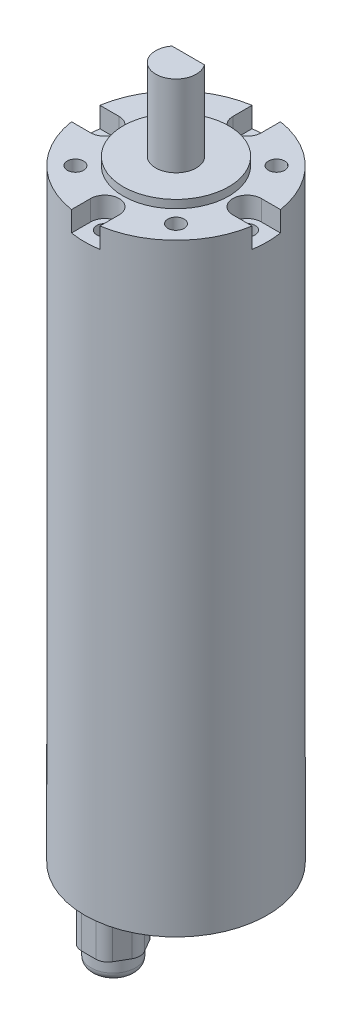
SolidWorks part; units mm, degrees
ref_plane "Front Plane" through (0, 0, 0) normal (0, 0, 1) x (1, 0, 0)
ref_plane "Top Plane" through (0, 0, 0) normal (0, 1, 0) x (1, 0, 0)
ref_plane "Right Plane" through (0, 0, 0) normal (1, 0, 0) x (0, 0, -1)
sketch "Sketch1" plane through (0, 0, 0) normal (0, 1, 0) x (1, 0, 0)
  circle A0 centre (0, 0) radius 22.5
  dimension "D1" = 45
extrude "Boss-Extrude1" add sketch "Sketch1" along normal blind 78
sketch "Sketch2" plane through (0, 78, 0) normal (0, 1, 0) x (1, 0, 0)
  circle A0 centre (0, 0) radius 22.5
  circle A1 centre (0, 0) radius 22.5 construction
extrude "Boss-Extrude2" add sketch "Sketch2" along normal blind 70.5
sketch "Sketch3" plane through (0, 148.5, 0) normal (0, 1, 0) x (1, 0, 0)
  circle A0 centre (0, 0) radius 13
  dimension "D1" = 26
extrude "Boss-Extrude3" add sketch "Sketch3" along normal blind 2
sketch "Sketch4" plane through (0, 150.5, 0) normal (0, 1, 0) x (1, 0, 0)
  line L0 (0, -5) -> (0, 3) construction
  line L1 (-4, 3) -> (4, 3)
  circle A0 centre (0, 0) radius 5
  dimension "D1" = 10
  dimension "D2" = 8
extrude "Boss-Extrude4" add sketch "Sketch4" along normal blind 20 contours A0 L0 L1 | L0 A0 L1 region at (-2.217, 150.5, 0.6334) region at (2.217, 150.5, 0.6334)
sketch "Sketch5" plane through (0, 150.5, 0) normal (0, 1, 0) x (1, 0, 0)
  circle A0 centre (0, 0) radius 5
  arc A1 (-4, 3) -> (4, 3) centre (0, 0) ccw construction
extrude "Boss-Extrude5" add sketch "Sketch5" along normal blind 7
sketch "Sketch6" plane through (0, 148.5, 0) normal (0, 1, 0) x (1, 0, 0)
  line L0 (0, 0) -> (0, 17.5) construction
  circle A0 centre (0, 0) radius 17.5 construction
  circle A1 centre (0, 17.5) radius 2
  circle A2 centre (12.3744, 12.3744) radius 2
  circle A3 centre (17.5, 0) radius 2
  circle A4 centre (12.3744, -12.3744) radius 2
  circle A5 centre (0, -17.5) radius 2
  circle A6 centre (-12.3744, -12.3744) radius 2
  circle A7 centre (-17.5, 0) radius 2
  circle A8 centre (-12.3744, 12.3744) radius 2
  point P5 (0, 0)
  point P6 (0, 0)
  point P7 (0, 0)
  point P22 (0, 0)
  point P23 (12.3744, 12.3744)
  dimension "D1" = 35
  dimension "D2" = 4
  dimension "D3" = 8
extrude "Cut-Extrude1" cut sketch "Sketch6" against normal blind 8 contours A8 | A2 | A4 | A6 region at (12.3744, 148.5, -12.3744) region at (12.3744, 148.5, 12.3744) region at (-12.3744, 148.5, 12.3744) region at (-12.3744, 148.5, -12.3744)
sketch "Sketch7" plane through (0, 148.5, 0) normal (0, 1, 0) x (1, 0, 0)
  line L0 (0, 0) -> (0, 22.5) construction
  line L1 (-3.5, 22.5) -> (3.5, 22.5)
  line L2 (-3.5, 22.5) -> (-3.5, 17.5)
  line L3 (-3.5, 17.5) -> (3.5, 17.5)
  line L4 (3.5, 22.5) -> (3.5, 17.5)
  line L5 (22.5, 3.5) -> (17.5, 3.5)
  line L6 (22.5, 3.5) -> (22.5, -3.5)
  line L7 (22.5, -3.5) -> (17.5, -3.5)
  line L8 (17.5, 3.5) -> (17.5, -3.5)
  line L9 (3.5, -22.5) -> (3.5, -17.5)
  line L10 (3.5, -22.5) -> (-3.5, -22.5)
  line L11 (-3.5, -22.5) -> (-3.5, -17.5)
  line L12 (3.5, -17.5) -> (-3.5, -17.5)
  line L13 (-22.5, -3.5) -> (-17.5, -3.5)
  line L14 (-22.5, -3.5) -> (-22.5, 3.5)
  line L15 (-22.5, 3.5) -> (-17.5, 3.5)
  line L16 (-17.5, -3.5) -> (-17.5, 3.5)
  circle A0 centre (0, 0) radius 22.5 construction
  circle A1 centre (0, 17.5) radius 3.5
  circle A2 centre (0, 0) radius 17.5 construction
  circle A3 centre (17.5, 0) radius 3.5
  circle A4 centre (0, -17.5) radius 3.5
  circle A5 centre (-17.5, 0) radius 3.5
  point P12 (0, 0)
  point P13 (0, 0)
  point P14 (0, 0)
  point P33 (0, 0)
  circle M14 centre (0, 0) radius 22.5
  dimension "D1" = 7
  dimension "D2" = 35
  dimension "D3" = 4
extrude "Cut-Extrude2" cut sketch "Sketch7" against normal blind 5 contours A3 L7 L5 M14 | L8 A3 | L8 A3 | A1 L4 L2 M14 | L3 A1 | L3 A1 | L16 A5 | L16 A5 | A5 L15 L13 M14 | L12 A4 | L12 A4 | A4 L11 L9 M14 region at (0, 148.5, -21.1892) region at (0, 148.5, -18.9854) region at (0, 148.5, -16.0146) region at (-21.1892, 148.5, 0) region at (21.1892, 148.5, 0) region at (-16.0146, 148.5, 0) region at (-18.9854, 148.5, 0) region at (18.9854, 148.5, 0) region at (16.0146, 148.5, 0) region at (0, 148.5, 21.1892) region at (0, 148.5, 16.0146) region at (0, 148.5, 18.9854)
sketch "Sketch8" plane through (0, 143.5, 0) normal (0, 1, 0) x (1, 0, 0)
  line L0 (0, 0) -> (0, 17.5) construction
  circle A0 centre (0, 0) radius 17.5 construction
  circle A1 centre (0, 17.5) radius 2
  circle A2 centre (17.5, 0) radius 2
  circle A3 centre (0, -17.5) radius 2
  circle A4 centre (-17.5, 0) radius 2
  point P5 (0, 0)
  point P6 (0, 0)
  point P7 (0, 0)
  point P14 (0, 0)
  point P15 (0, 0)
  dimension "D1" = 35
  dimension "D2" = 4
  dimension "D3" = 4
extrude "Cut-Extrude3" cut sketch "Sketch8" against normal blind 8
sketch "Sketch9" plane through (0, 0, 0) normal (0, -1, 0) x (1, 0, 0)
  line L0 (0, 0) -> (0, 22.5) construction
  line L1 (-3.5, 21.5) -> (3.5, 21.5)
  line L2 (-3.5, 21.5) -> (-7, 15.4378)
  line L3 (-7, 15.4378) -> (-3.5, 9.3756)
  line L4 (-3.5, 9.3756) -> (3.5, 9.3756)
  line L5 (3.5, 9.3756) -> (7, 15.4378)
  line L6 (7, 15.4378) -> (3.5, 21.5)
  circle A0 centre (0, 0) radius 22.5 construction
  point P7 (0, 21.5)
  point P12 (0, 0)
  point P13 (6.7955, 15.9949)
  dimension "D1" = 1
  dimension "D2" = 120
  dimension "D3" = 7
extrude "Boss-Extrude6" add sketch "Sketch9" along normal blind 9
sketch "Sketch10" plane through (0, -9, 0) normal (0, -1, 0) x (1, 0, 0)
  line L0 (-7, 15.4378) -> (7, 15.4378) construction
  circle A0 centre (0, 15.4378) radius 5.5
  point P6 (0, 0)
  dimension "D1" = 11
extrude "Boss-Extrude7" add sketch "Sketch10" along normal blind 5
fillet "Fillet1" radius 3 6 edges at (-3.5, -4.5, 21.5) (3.5, -4.5, 21.5) (7, -4.5, 15.4378) (3.5, -4.5, 9.3756) (-3.5, -4.5, 9.3756) (-7, -4.5, 15.4378)
fillet "Fillet2" radius 2 1 edges at (0, -14, 9.9378)
sketch "Sketch11" plane through (0, 0, 0) normal (0, -1, 0) x (1, 0, 0)
  circle A0 centre (0, 0) radius 5.5
  dimension "D1" = 11
extrude "Boss-Extrude8" add sketch "Sketch11" along normal blind 1
fillet "Fillet3" radius 1 1 edges at (0, -1, -5.5)
